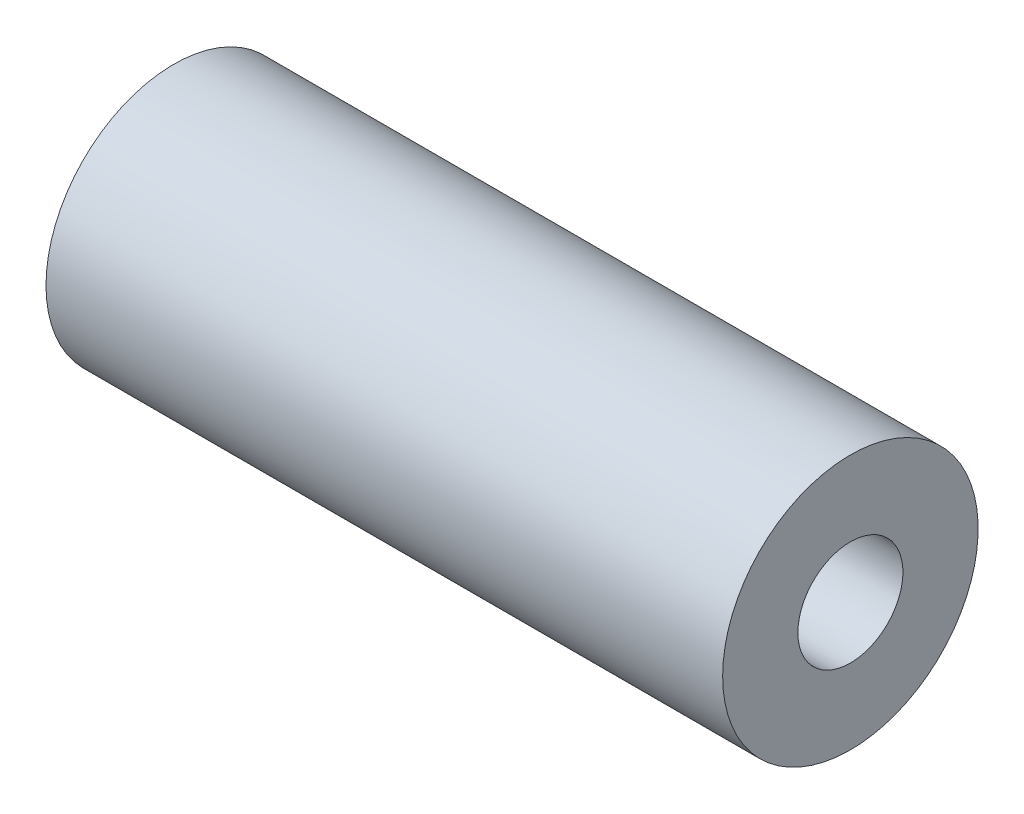
SolidWorks part; units mm, degrees
ref_plane "Front Plane" through (0, 0, 0) normal (0, 0, 1) x (1, 0, 0)
ref_plane "Top Plane" through (0, 0, 0) normal (0, 1, 0) x (1, 0, 0)
ref_plane "Right Plane" through (0, 0, 0) normal (1, 0, 0) x (0, 0, -1)
sketch "Union_T4 Sketch" plane through (0, 0, 0) normal (0, 0, 1) x (1, 0, 0)
  line L0 (-1000, 0) -> (1000, 0) construction
  line L1 (-20.45, 0) -> (-20.45, 7.722)
  line L2 (-20.45, 7.722) -> (-3.45, 7.722)
  line L3 (-3.45, 7.722) -> (3.45, 7.722)
  line L4 (3.45, 7.722) -> (20.45, 7.722)
  line L5 (20.45, 7.722) -> (20.45, 0)
  line L6 (20.45, 0) -> (-20.45, 0)
revolve "Union_T4" add sketch "Union_T4 Sketch" angle 360 about L0
ref_axis "Engine Axis" through (22.495, 0, 0) along (-1, 0, 0)
sketch "Socket 1 Sketch" plane through (0, 0, 0) normal (0, 0, 1) x (1, 0, 0)
  line L0 (-1000, 0) -> (1000, 0) construction
  line L1 (-21.45, 0) -> (-21.45, 3.175)
  line L2 (-21.45, 3.175) -> (-5.25, 3.175)
  line L3 (-5.25, 3.175) -> (-5.25, 0)
  line L4 (-5.25, 0) -> (-21.45, 0)
revolve "Socket 1" cut sketch "Socket 1 Sketch" angle 360 about L0
sketch "Socket 2 Sketch" plane through (0, 0, 0) normal (0, 0, 1) x (1, 0, 0)
  line L0 (-1000, 0) -> (1000, 0) construction
  line L1 (5.25, 0) -> (5.25, 3.175)
  line L2 (5.25, 3.175) -> (21.45, 3.175)
  line L3 (21.45, 3.175) -> (21.45, 0)
  line L4 (21.45, 0) -> (5.25, 0)
revolve "Socket 2" cut sketch "Socket 2 Sketch" angle 360 about L0
